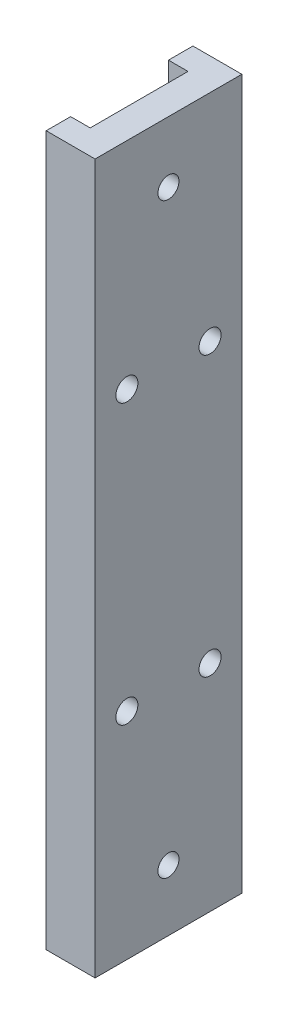
SolidWorks part; units mm, degrees
ref_plane "Front Plane" through (0, 0, 0) normal (0, 0, 1) x (1, 0, 0)
ref_plane "Top Plane" through (0, 0, 0) normal (0, 1, 0) x (1, 0, 0)
ref_plane "Right Plane" through (0, 0, 0) normal (1, 0, 0) x (0, 0, -1)
ref_plane "Plane1" through (0, 260, 0) normal (0, -1, 0) x (-1, 0, 0)
sketch "Sketch1" plane through (0, 260, 0) normal (0, -1, 0) x (-1, 0, 0)
  line L0 (71.5, -127.5) -> (61.5, -127.5)
  line L1 (61.5, -127.5) -> (61.5, -97.5)
  line L2 (61.5, -97.5) -> (71.5, -97.5)
  line L3 (71.5, -97.5) -> (71.5, -102.5)
  line L4 (71.5, -102.5) -> (67.5, -102.5)
  line L5 (67.5, -102.5) -> (67.5, -122.5)
  line L6 (67.5, -122.5) -> (71.5, -122.5)
  line L7 (71.5, -122.5) -> (71.5, -127.5)
  line L8 (68.9986, -122.5) -> (74.3631, -122.5) construction
  line L9 (68.9986, -102.5) -> (74.3631, -102.5) construction
  line L10 (67.5, -115.6369) -> (67.5, -121.0014) construction
  dimension "D1" = 5
  dimension "D2" = 10
  dimension "D3" = 6
extrude "Boss-Extrude1" add sketch "Sketch1" along normal blind 145
sketch "Sketch5" plane through (-61.5, 0, 0) normal (1, 0, 0) x (0, 0, -1)
  line L0 (-97.5, 260) -> (-127.5, 260) construction
  line L1 (-121, 159) -> (-104, 159) construction
  line L2 (-121, 159) -> (-121, 216) construction
  line L3 (-121, 216) -> (-104, 216) construction
  line L4 (-104, 159) -> (-104, 216) construction
  line L5 (-121, 159) -> (-104, 216) construction
  line L6 (-121, 216) -> (-104, 159) construction
  line L7 (-97.5, 115) -> (-97.5, 260) construction
  point P0 (-112.5, 187.5)
  point P8 (-112.5, 260)
  point P11 (-97.5, 187.5)
  dimension "D1" = 17
  dimension "D2" = 57
hole_wizard "M4 Clearance Hole1" positions "Sketch2" profile "Sketch4" hole size "M4" standard "ISO" end condition through all
sketch "Sketch2" plane through (-61.5, 0, 0) normal (1, 0, 0) x (0, 0, -1)
  line L0 (-112.5, 247.5) -> (-112.5, 127.5) construction
  line L2 (-97.5, 260) -> (-127.5, 260) construction
  line L4 (-112.5, 247.5) -> (-112.5, 260) construction
  line L7 (-112.5, 127.5) -> (-112.5, 115) construction
  line L8 (-97.5, 115) -> (-127.5, 115) construction
  point P1 (-112.5, 247.5)
  point P2 (-112.5, 127.5)
  point P7 (-112.5, 260)
  dimension "D1" = 120
sketch "Sketch4" plane through (-61.5, 247.5, 112.5) normal (0, 1, 0) x (0, 0, -1)
  line L0 (0, 0) -> (0, 10)
  line L1 (0, 10) -> (2.15, 10)
  line L2 (2.15, 10) -> (2.15, 0)
  line L5 (2.15, 0) -> (0, 0)
  line L11 (0, -6.35) -> (0, 107.95) construction
  dimension "Thru Hole Dia." = 4.3
  dimension "Thru Hole Depth" = 10
hole_wizard "Hole1" positions "Sketch6" profile "Sketch7" legacy
sketch "Sketch6" plane through (-61.5, 0, 0) normal (1, 0, 0) x (0, 0, -1)
  point P0 (-104, 216)
  point P3 (-121, 216)
  point P6 (-104, 159)
  point P9 (-121, 159)
sketch "Sketch7" plane through (-61.5, 216, 104) normal (0, 1, 0) x (0, 0, -1)
  line L0 (0, 0) -> (0, 6)
  line L1 (0, 6) -> (2.25, 6)
  line L2 (2.25, 6) -> (2.25, 0)
  line L3 (2.25, 0) -> (0, 0)
  line L4 (0, 110) -> (0, -10) construction
  dimension "Diameter" = 4.5
  dimension "Depth" = 6
